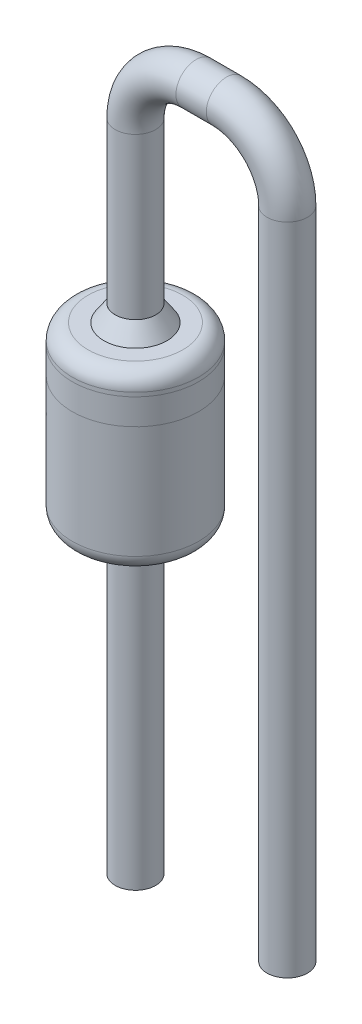
SolidWorks part; units mm, degrees
ref_plane "Front Plane" through (0, 0, 0) normal (0, 0, 1) x (1, 0, 0)
ref_plane "Top Plane" through (0, 0, 0) normal (0, 1, 0) x (1, 0, 0)
ref_plane "Right Plane" through (0, 0, 0) normal (1, 0, 0) x (0, 0, -1)
ref_plane "BODY_RPlane" through (0, 0, 0) normal (1, 0, 0) x (0, 0, -1)
sketch "Sketch10" plane through (0, 0, 0) normal (0, 0, 1) x (1, 0, 0)
  line L1 (-0.5944, 3.39) -> (-0.3963, 3.39)
  line L3 (0, 2.3) -> (-0.7925, 2.3) construction
  line L12 (-0.7925, 1.4081) -> (-0.7925, 3.1919)
  line L14 (-0.7076, 1.21) -> (-0.1163, 1.21) construction
  line L15 (-0.3962, 1.21) -> (-0.3962, 2.3) construction
  line L16 (-0.5944, 1.21) -> (-0.3962, 1.21)
  line L17 (-0.3962, 1.21) -> (-0.3963, 3.39)
  line L18 (0, 1) -> (0, 3.6) construction
  arc A6 (-0.7925, 1.4081) -> (-0.5944, 1.21) centre (-0.5944, 1.4081) ccw
  arc A8 (-0.7925, 3.1919) -> (-0.5944, 3.39) centre (-0.5944, 3.1919) cw
  point P22 (0, 2.3)
  point P30 (-0.7925, 2.3)
  point P31 (-0.3962, 2.3)
  point P34 (-0.7925, 2.3)
  dimension "D1" = 2.6
  dimension "D8" = 0.1981
  dimension "D7" = 0.7925
  dimension "D9" = 0.21
  dimension "D10" = 0.3962
  dimension "D2" = 2.3
revolve "BODY_main" add sketch "Sketch10" angle 360 about L18
sketch "Sketch11" plane through (0, 0, 0) normal (0, 0, 1) x (1, 0, 0)
  line L4 (0, 1.21) -> (0, 1)
  line L17 (-200000.7076, 1.21) -> (199999.8837, 1.21) construction
  line L18 (0, 1) -> (0, 3.6) construction
  line L19 (0, 1) -> (-0.254, 1)
  line L20 (-0.254, 1) -> (-0.3962, 1.21)
  line L21 (-0.3962, 1.21) -> (0, 1.21)
  line L22 (-0.7925, 2.3) -> (0, 2.3) construction
  line L23 (-0.3962, 3.39) -> (0, 3.39)
  line L24 (-0.254, 3.6) -> (-0.3962, 3.39)
  line L25 (0, 3.6) -> (-0.254, 3.6)
  line L26 (0, 3.39) -> (0, 3.6)
  dimension "D3" = 0.254
revolve "BODY_to_PIN" add sketch "Sketch11" angle 360 about L18
ref_plane "TEXT_plane" through (-0.8925, 0, 0) normal (1, 0, 0) x (0, 0, -1)
sketch "Sketch4"
  dimension "D1" = 4.9794
  dimension "D3" = 0.325
  dimension "D5" = 0.05
  dimension "D6" = 0.15
  dimension "D2" = 5
wrap "TEXT_Wrap" sketch "Sketch4" wrap type scribe source sketch "Sketch4" face at (0.7925, 1.4081, 0)
sketch "Sketch6" plane through (1, 1, 0) normal (0, 1, 0) x (0, 0, -1)
  circle A0 centre (0, 1) radius 0.254
  dimension "D1" = 0.508
sketch "Sketch7" plane through (0, 0, 0) normal (0, 0, 1) x (1, 0, 0)
  line L0 (1.143, 6.3746) -> (0.762, 6.3746)
  line L1 (0, 5.6126) -> (0, -2.6)
  line L2 (0.9525, 6.3746) -> (0.9525, -2.6) construction
  line L3 (0, -2.6) -> (0.9525, -2.6) construction
  line L5 (0, 5.6126) -> (0, 3.6)
  line L6 (1.905, 5.6126) -> (1.905, -2.6)
  line L7 (0, -4.1102) -> (0, 4.1102) construction
  line L8 (0.254, 3.6) -> (-0.254, 3.6) construction
  arc A0 (0.762, 6.3746) -> (0, 5.6126) centre (0.762, 5.6126) ccw
  arc A1 (1.143, 6.3746) -> (1.905, 5.6126) centre (1.143, 5.6126) cw
  point P11 (0, 3.6)
  dimension "D3" = 0.762
  dimension "D1" = 2.6
sweep "PINS" add profiles "Sketch6" path "Sketch7"
equation "\"D4@Sketch7\"=\"PIN_PITCH\""
equation "\"pin_config-----------------\"= 0x000000000000000000000000000000000"
equation "\"PIN_PITCH\"= 75mil"
equation "\"PCB_standoff\"= 1mm"
equation "\"PCB_thickness\"= 1.6mm"
equation "\"PCB_bottom_lead\"= 1.0mm"
equation "\"PIN_C_max\"= 0.558mm"
equation "\"PIN_C_min\"= 0.458mm"
equation "\"body_config----------------\"= 0x000000000000000000000000000000000"
equation "\"BODY_B_max\"= 3.04mm"
equation "\"BODY_B_min\"= 2.16mm"
equation "\"BODY_D_max\"= 1.9mm"
equation "\"BODY_D_min\"= 1.27mm"
equation "\"part_config----------------\"= 0x000000000000000000000000000000000"
equation "\"Component_Size\"= 1"
equation "\"Component_Type\"= 0'variable is not used"
equation "\"D1@TEXT_plane\"=\"BODY_D\"/2 + 0.1"
equation "\"D1@Sketch4\"=\"BODY_D\" * pi"
equation "\"D1@Sketch6\"=\"PIN_C\""
equation "\"D3@Sketch7\"=\"PIN_R\""
equation "\"D1@Sketch7\"=\"PIN_L\""
equation "\"D3@Sketch4\"=\"BODY_CATM_H1\""
equation "\"D1@Sketch10\"=\"BODY_B\""
equation "\"D7@Sketch10\"=\"BODY_D\"/2"
equation "\"D8@Sketch10\"=\"BODY_D\"/8"
equation "\"D10@Sketch10\"=\"BODY_D\"/4"
equation "\"D2@Sketch10\"=\"BODY_B\"/2 + \"PCB_standoff\""
equation "\"D3@Sketch11\"=\"PIN_C\"/2"
equation "\"PIN_A_min\"= 13mm"
equation "\"auto_calc-------------------\"= 0x000000000000000000000000000000000"
equation "\"BODY_B\"= IIF ( \"Component_Size\" > 0 , IIF ( \"Component_Size\" = 1 , ( ( \"BODY_B_max\" + \"BODY_B_min\" ) / 2 ) , \"BODY_B_max\" ) , \"BODY_B_min\" )'NOT_FOR_USER , AUTOMATIC CALCULATION"
equation "\"BODY_D\"= IIF ( \"Component_Size\" > 0 , IIF ( \"Component_Size\" = 1 , ( ( \"BODY_D_max\" + \"BODY_D_min\" ) / 2 ) , \"BODY_D_max\" ) , \"BODY_D_min\" )'NOT_FOR_USER , AUTOMATIC CALCULATION"
equation "\"PIN_C\"= IIF ( \"Component_Size\" > 0 , IIF ( \"Component_Size\" = 1 , ( ( \"PIN_C_max\" + \"PIN_C_min\" ) / 2 ) , \"PIN_C_max\" ) , \"PIN_C_min\" )'NOT_FOR_USER , AUTOMATIC CALCULATION"
equation "\"PIN_L\"= \"PCB_thickness\" + \"PCB_bottom_lead\"'NOT_FOR_USER , AUTOMATIC CALCULATION"
equation "\"PIN_R\"= \"PIN_C\" * 1.5'NOT_FOR_USER , AUTOMATIC CALCULATION"
equation "\"BODY_CATM_H1\"= \"BODY_B\" / 8'NOT_FOR_USER , AUTOMATIC CALCULATION"
equation "\"D5@Sketch7\"=\"PIN_A_min\""
